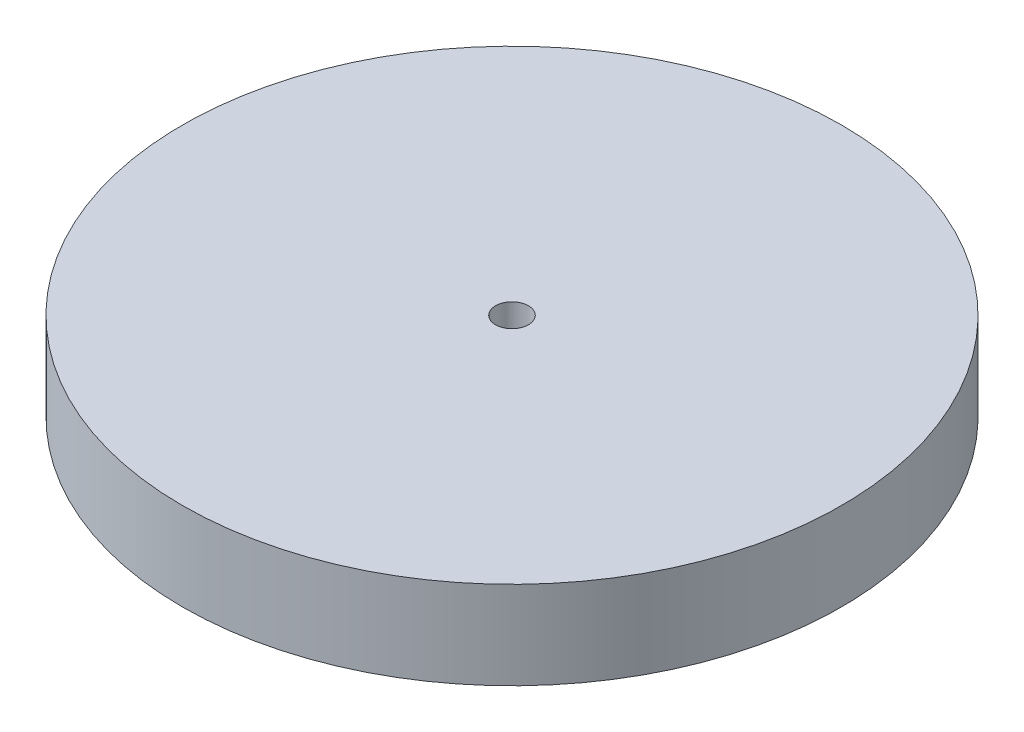
SolidWorks part; units mm, degrees
ref_plane "Front Plane" through (0, 0, 0) normal (0, 0, 1) x (1, 0, 0)
ref_plane "Top Plane" through (0, 0, 0) normal (0, 1, 0) x (1, 0, 0)
ref_plane "Right Plane" through (0, 0, 0) normal (1, 0, 0) x (0, 0, -1)
sketch "Sketch1" plane through (0, 0, 0) normal (0, 1, 0) x (1, 0, 0)
  circle A0 centre (0, 0) radius 30
  circle A1 centre (0, 0) radius 1.5
  dimension "D1" = 60
  dimension "D2" = 3
extrude "Boss-Extrude1" add sketch "Sketch1" along normal blind 8
